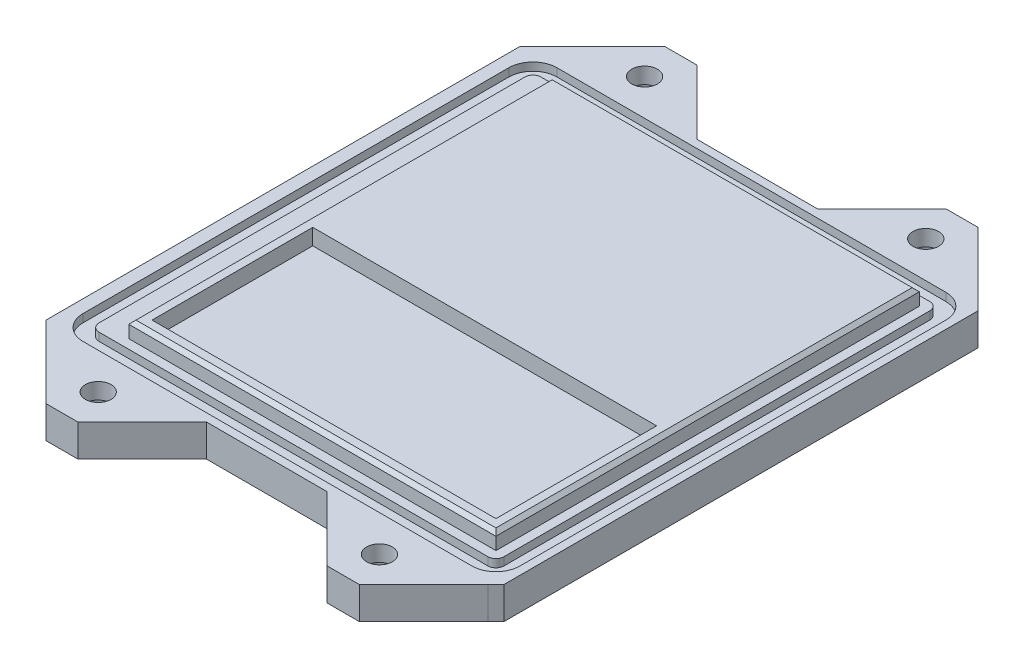
SolidWorks part; units mm, degrees
ref_plane "Front Plane" through (0, 0, 0) normal (0, 0, 1) x (1, 0, 0)
ref_plane "Top Plane" through (0, 0, 0) normal (0, 1, 0) x (1, 0, 0)
ref_plane "Right Plane" through (0, 0, 0) normal (1, 0, 0) x (0, 0, -1)
sketch "Sketch2" plane through (0, 0, 0) normal (0, 1, 0) x (1, 0, 0)
  line L1 (-44.7854, -24.8803) -> (11.2146, -24.8803)
  line L2 (-44.7854, -24.8803) -> (-44.7854, 36.1197)
  line L3 (-44.7854, 36.1197) -> (11.2146, 36.1197)
  line L4 (11.2146, -24.8803) -> (11.2146, 36.1197)
  dimension "D1" = 61
  dimension "D2" = 56
extrude "Boss-Extrude1" add sketch "Sketch2" along normal mid plane 4
sketch "Sketch3" plane through (0, 2, 0) normal (0, 1, 0) x (1, 0, 0)
  line L1 (-38.7854, 32.1197) -> (7.2146, 32.1197)
  line L2 (-38.7854, 32.1197) -> (-38.7854, -20.8803)
  line L3 (-38.7854, -20.8803) -> (7.2146, -20.8803)
  line L4 (7.2146, 32.1197) -> (7.2146, -20.8803)
  dimension "D1" = 4
  dimension "D2" = 4
  dimension "D3" = 6
  dimension "D4" = 4
extrude "Boss-Extrude4" add sketch "Sketch3" along normal blind 2
sketch "Sketch4" plane through (-44.7854, 0, 0) normal (-1, 0, 0) x (0, 0, 1)
  line L1 (-36.1197, -2) -> (24.8803, -2)
  line L2 (-36.1197, -2) -> (-36.1197, 2)
  line L3 (-36.1197, 2) -> (24.8803, 2)
  line L4 (24.8803, -2) -> (24.8803, 2)
extrude "Boss-Extrude5" add sketch "Sketch4" along normal blind 1
sketch "Sketch5" plane through (0, -2, 0) normal (0, -1, 0) x (1, 0, 0)
  line L0 (11.2146, -36.1197) -> (-45.7854, -36.1197) construction
  line L1 (3.2146, -36.1197) -> (-2.7854, -36.1197)
  line L2 (3.2146, -36.1197) -> (3.2146, -43.1197)
  line L3 (3.2146, -43.1197) -> (-2.7854, -43.1197)
  line L4 (-2.7854, -36.1197) -> (-2.7854, -43.1197)
  line L5 (-45.7854, 24.8803) -> (11.2146, 24.8803) construction
  line L6 (-37.7854, -36.1197) -> (-31.7854, -36.1197)
  line L7 (-37.7854, -36.1197) -> (-37.7854, -43.1197)
  line L8 (-37.7854, -43.1197) -> (-31.7854, -43.1197)
  line L9 (-31.7854, -36.1197) -> (-31.7854, -43.1197)
  line L10 (3.2146, 24.8803) -> (-2.7854, 24.8803)
  line L11 (3.2146, 24.8803) -> (3.2146, 31.8803)
  line L12 (3.2146, 31.8803) -> (-2.7854, 31.8803)
  line L13 (-2.7854, 24.8803) -> (-2.7854, 31.8803)
  line L15 (-37.7854, 24.8803) -> (-31.7854, 24.8803)
  line L16 (-37.7854, 24.8803) -> (-37.7854, 31.8803)
  line L17 (-37.7854, 31.8803) -> (-31.7854, 31.8803)
  line L18 (-31.7854, 24.8803) -> (-31.7854, 31.8803)
  circle A0 centre (0.2146, -39.6197) radius 1.6
  circle A1 centre (-34.7854, -39.6197) radius 1.6
  circle A2 centre (-34.7854, 28.3803) radius 1.6
  circle A3 centre (0.2146, 28.3803) radius 1.6
  dimension "D4" = 3
  dimension "D9" = 3.2
  dimension "D10" = 3.2
  dimension "D17" = 3.2
  dimension "D18" = 3.2
  dimension "D1" = 8
  dimension "D2" = 6
  dimension "D3" = 7
  dimension "D5" = 3.5
  dimension "D6" = 8
  dimension "D7" = 7
  dimension "D8" = 6
  dimension "D11" = 8
  dimension "D12" = 8
  dimension "D13" = 6
  dimension "D14" = 6
  dimension "D15" = 7
  dimension "D16" = 7
extrude "Boss-Extrude7" add sketch "Sketch5" against normal blind 4
sketch "Sketch10" plane through (0, 2, 0) normal (0, 1, 0) x (1, 0, 0)
  line L0 (6.1446, -23.8803) -> (7.1799, -23.8803)
  line L1 (6.1446, -23.8803) -> (-44.1854, -23.8803)
  line L3 (5.8967, -21.8803) -> (-42.1854, -21.8803)
  line L4 (-44.1854, -23.8803) -> (-44.1854, -21.4264)
  line L6 (-42.1854, -21.8803) -> (-42.1854, 33.1197)
  line L7 (-41.0657, 35.1197) -> (-44.1854, 35.1197)
  line L8 (-44.1854, -21.4264) -> (-44.1854, 35.1197)
  line L9 (-41.0657, 35.1197) -> (10.2146, 35.1197)
  line L11 (-42.1854, 33.1197) -> (8.2146, 33.1197)
  line L12 (10.2146, 35.1197) -> (10.2146, 33.0745)
  line L14 (10.2146, 33.0745) -> (10.2146, -23.8803)
  line L15 (10.2146, -23.8803) -> (7.1799, -23.8803)
  line L16 (8.2146, 33.1197) -> (8.2146, -21.8803)
  line L17 (5.8967, -21.8803) -> (8.2146, -21.8803)
  dimension "D1" = 2
  dimension "D2" = 2
  dimension "D3" = 2
  dimension "D4" = 2
  dimension "D5" = 2
  dimension "D6" = 1.6
  dimension "D7" = 1
  dimension "D8" = 1
  dimension "D9" = 1
extrude "Cut-Extrude1" cut sketch "Sketch10" against normal blind 1
sketch "r" plane through (0, -2, 0) normal (0, -1, 0) x (1, 0, 0)
  text T0 "XB1"
extrude "Cut-Extrude2" [suppressed] cut sketch "r" against normal blind 0.1
chamfer "Chamfer1" distance 7 angle 45 1 edges at (3.2146, 0, -36.1197)
chamfer "Chamfer2" distance 7 angle 45 1 edges at (-2.7854, 0, -36.1197)
chamfer "Chamfer3" distance 7 angle 45 6 edges at (-2.7854, 0, 24.8803) (3.2146, 0, 24.8803) (-31.7854, 0, 24.8803) (-37.7854, 0, 24.8803) (-37.7854, 0, -36.1197) (-31.7854, 0, -36.1197)
sketch "Sketch11" plane through (0, -2, 0) normal (0, -1, 0) x (1, 0, 0)
  circle A0 centre (-34.7854, 28.3803) radius 3.1
  circle A1 centre (0.2146, 28.3803) radius 3.1
  circle A2 centre (0.2146, -39.6197) radius 3.1
  circle A3 centre (-34.7854, -39.6197) radius 3.1
  dimension "D1" = 6.2
extrude "Cut-Extrude3" cut sketch "Sketch11" against normal blind 2
chamfer "Chamfer4" [suppressed] distance 1 angle 45
chamfer "Chamfer5" distance 1 angle 45 4 edges at (-45.7854, 0, -36.1197) (11.2146, 0, -36.1197) (11.2146, 0, 24.8803) (-45.7854, 0, 24.8803)
sketch "Sketch12" plane through (0, -2, 0) normal (0, -1, 0) x (1, 0, 0)
  line L0 (-31.7854, 31.8803) -> (-32.7854, 32.8803)
  line L1 (-37.7854, 31.8803) -> (-36.7854, 32.8803)
  line L2 (-32.7854, 32.8803) -> (-36.7854, 32.8803)
  line L3 (-37.7854, 31.8803) -> (-31.7854, 31.8803)
  line L4 (3.2146, 31.8803) -> (2.2146, 32.8803)
  line L5 (-2.7854, 31.8803) -> (-1.7854, 32.8803)
  line L6 (3.2146, 31.8803) -> (-2.7854, 31.8803)
  line L7 (-1.7854, 32.8803) -> (2.2146, 32.8803)
  line L8 (-2.7854, -43.1197) -> (-1.7854, -44.1197)
  line L9 (-1.0098, -44.1197) -> (2.2146, -44.1197)
  line L10 (3.2146, -43.1197) -> (2.2146, -44.1197)
  line L11 (-1.0098, -44.1197) -> (-1.7854, -44.1197)
  line L12 (-2.7854, -43.1197) -> (3.2146, -43.1197)
  line L13 (-31.7854, -43.1197) -> (-32.7854, -44.1197)
  line L14 (-37.7854, -43.1197) -> (-36.7854, -44.1197)
  line L15 (-36.7854, -44.1197) -> (-32.7854, -44.1197)
  line L16 (-37.7854, -43.1197) -> (-31.7854, -43.1197)
extrude "Boss-Extrude8" add sketch "Sketch12" against normal blind 4
sketch "Sketch13" plane through (0, 4, 0) normal (0, 1, 0) x (1, 0, 0)
  line L0 (7.2146, 32.1197) -> (-38.7854, 32.1197) construction
  line L1 (-38.7854, -20.8803) -> (-38.6854, -20.8803)
  line L2 (-38.7854, -20.8803) -> (-38.7854, 32.1197)
  line L3 (-38.7854, 32.1197) -> (-38.6854, 32.1197)
  line L4 (-38.6854, -20.7803) -> (-38.6854, 32.0197)
  line L6 (7.2146, -20.8803) -> (-38.6854, -20.8803)
  line L7 (7.2146, -20.8803) -> (7.2146, -20.7803)
  line L8 (7.1146, -20.7803) -> (-38.6854, -20.7803)
  line L10 (7.2146, 32.1197) -> (-38.6854, 32.1197)
  line L11 (7.2146, 32.1197) -> (7.2146, 32.0197)
  line L12 (7.1146, 32.0197) -> (-38.6854, 32.0197)
  line L15 (7.2146, -20.7803) -> (7.2146, 32.0197)
  line L17 (7.1146, -20.7803) -> (7.1146, 32.0197)
  dimension "D1" = 0.1
  dimension "D2" = 0.1
  dimension "D3" = 0.1
  dimension "D4" = 0.1
extrude "Cut-Extrude4" cut sketch "Sketch13" against normal blind 2
chamfer "Chamfer6" distance 0.5 angle 45 4 edges at (-15.7854, 4, -32.0197) (7.1146, 4, -5.6197) (-15.7854, 4, 20.7803) (-38.6854, 4, -5.6197)
sketch "Sketch14" plane through (0, -2, 0) normal (0, -1, 0) x (1, 0, 0)
  line L1 (-41.7854, -4.8197) -> (-39.5561, -4.8197)
  line L2 (-41.7854, -4.8197) -> (-41.7854, -6.4197)
  line L3 (-41.7854, -6.4197) -> (-39.5561, -6.4197)
  line L4 (-39.5561, -4.8197) -> (-39.5561, -6.4197)
  line L6 (-45.7854, -35.1197) -> (-45.7854, 23.8803) construction
  point P4 (-41.7854, -5.6197)
  point P7 (-45.7854, -5.6197)
  dimension "D1" = 1.6
  dimension "D2" = 0
  dimension "D3" = 4
extrude "Cut-Extrude5" cut sketch "Sketch14" against normal blind 0.4
chamfer "Chamfer7" distance 0.4 angle 45 4 edges at (-40.6707, -1.6, -4.8197) (-39.5561, -1.6, -5.6197) (-40.6707, -1.6, -6.4197) (-41.7854, -1.6, -5.6197)
sketch "Sketch15" plane through (0, 4, 0) normal (0, 1, 0) x (1, 0, 0)
  line L1 (-37.1854, -19.2803) -> (5.6146, -19.2803)
  line L2 (-37.1854, -19.2803) -> (-37.1854, 0.7197)
  line L3 (-37.1854, 0.7197) -> (5.6146, 0.7197)
  line L4 (5.6146, -19.2803) -> (5.6146, 0.7197)
  dimension "D1" = 1
  dimension "D2" = 1
  dimension "D3" = 1
  dimension "D4" = 20
extrude "Cut-Extrude6" cut sketch "Sketch15" against normal blind 2
sketch "Sketch17" plane through (0, 4, 0) normal (0, 1, 0) x (1, 0, 0)
  line L1 (7.0646, 31.9697) -> (-38.6354, 31.9697)
  line L2 (7.0646, 31.9697) -> (7.0646, -20.7303)
  line L3 (7.0646, -20.7303) -> (-38.6354, -20.7303)
  line L4 (-38.6354, 31.9697) -> (-38.6354, -20.7303)
  line L5 (39.6903, 50.7811) -> (-65.6876, 50.7811)
  line L6 (39.6903, 50.7811) -> (39.6903, -39.604)
  line L7 (39.6903, -39.604) -> (-65.6876, -39.604)
  line L8 (-65.6876, 50.7811) -> (-65.6876, -39.604)
  dimension "D1" = 52.75
  dimension "D2" = 45.7
  dimension "D3" = 45.75
  dimension "D4" = 52.7
extrude "Cut-Extrude7" cut sketch "Sketch17" against normal blind 2
fillet "Fillet1" radius 3 4 edges at (-44.1854, 1.5, 23.8803) (10.2146, 1.5, 23.8803) (10.2146, 1.5, -35.1197) (-44.1854, 1.5, -35.1197)
sketch "Sketch18" plane through (0, -2, 0) normal (0, -1, 0) x (1, 0, 0)
  line L0 (-9.7854, -36.1197) -> (-24.7854, -36.1197) construction
  line L1 (-45.7854, -34.1197) -> (11.2146, -34.1197)
  line L2 (-47.893, -34.1197) -> (-47.893, -33.1197)
  line L3 (-45.7854, -33.1197) -> (11.2158, -33.1197)
  line L5 (-45.7854, -30.1197) -> (11.2193, -30.1197)
  line L6 (-45.7854, -29.1197) -> (11.2205, -29.1197)
  line L7 (-45.7854, -26.1197) -> (11.224, -26.1197)
  line L8 (-45.7854, -25.1197) -> (11.2252, -25.1197)
  line L9 (-45.7854, -22.1197) -> (11.2287, -22.1197)
  line L10 (-45.7854, -21.1197) -> (11.2298, -21.1197)
  line L11 (-45.7854, -18.1197) -> (11.2333, -18.1197)
  line L12 (-45.7854, -17.1197) -> (11.2345, -17.1197)
  line L13 (-45.7854, -14.1197) -> (11.238, -14.1197)
  line L14 (-45.7854, -13.1197) -> (11.2392, -13.1197)
  line L15 (-45.7854, -10.1197) -> (11.2427, -10.1197)
  line L16 (-45.7854, -9.1197) -> (11.2439, -9.1197)
  line L17 (-45.7854, -6.1197) -> (11.2474, -6.1197)
  line L18 (-45.7854, -5.1197) -> (11.2485, -5.1197)
  line L19 (-45.7854, -2.1197) -> (11.252, -2.1197)
  line L20 (-45.7854, -1.1197) -> (11.2532, -1.1197)
  line L21 (-45.7854, 1.8803) -> (11.2567, 1.8803)
  line L22 (-45.7854, 2.8803) -> (11.2579, 2.8803)
  line L23 (-45.7854, 5.8803) -> (11.2614, 5.8803)
  line L24 (-45.7854, 6.8803) -> (11.2626, 6.8803)
  line L25 (-45.7854, 9.8803) -> (11.2661, 9.8803)
  line L26 (-45.7854, 10.8803) -> (11.2672, 10.8803)
  line L27 (-45.7854, 13.8803) -> (11.2707, 13.8803)
  line L28 (-45.7854, 14.8803) -> (11.2719, 14.8803)
  line L29 (-45.7854, 17.8803) -> (11.2754, 17.8803)
  line L30 (-45.7854, 18.8803) -> (11.2766, 18.8803)
  line L31 (-45.7854, 21.8803) -> (11.2801, 21.8803)
  line L32 (-45.7854, 22.8803) -> (11.2813, 22.8803)
  line L36 (-39.5561, -6.1197) -> (-39.5561, -5.1197)
  line L37 (-45.7854, -34.1197) -> (-45.7854, -33.1197)
  line L38 (-45.7854, -35.1197) -> (-45.7854, 23.8803) construction
  line L39 (11.2813, 22.8803) -> (11.2801, 21.8803)
  line L40 (11.2146, 23.8803) -> (11.2146, -35.1197) construction
  line L41 (-45.7854, -30.1197) -> (-45.7854, -29.1197)
  line L42 (-45.7854, -26.1197) -> (-45.7854, -25.1197)
  line L43 (-45.7854, -22.1197) -> (-45.7854, -21.1197)
  line L44 (-45.7854, -18.1197) -> (-45.7854, -17.1197)
  line L45 (-45.7854, -14.1197) -> (-45.7854, -13.1197)
  line L46 (-45.7854, -10.1197) -> (-45.7854, -9.1197)
  line L47 (-45.7854, -6.1197) -> (-45.7854, -5.1197)
  line L48 (-45.7854, -2.1197) -> (-45.7854, -1.1197)
  line L49 (-45.7854, 1.8803) -> (-45.7854, 2.8803)
  line L50 (-45.7854, 5.8803) -> (-45.7854, 6.8803)
  line L51 (-45.7854, 9.8803) -> (-45.7854, 10.8803)
  line L52 (-45.7854, 13.8803) -> (-45.7854, 14.8803)
  line L53 (-45.7854, 17.8803) -> (-45.7854, 18.8803)
  line L54 (-45.7854, 21.8803) -> (-45.7854, 22.8803)
  line L55 (11.2766, 18.8803) -> (11.2754, 17.8803)
  line L56 (11.2719, 14.8803) -> (11.2707, 13.8803)
  line L57 (11.2672, 10.8803) -> (11.2661, 9.8803)
  line L58 (11.2626, 6.8803) -> (11.2614, 5.8803)
  line L59 (11.2532, -1.1197) -> (11.252, -2.1197)
  line L60 (11.2485, -5.1197) -> (11.2474, -6.1197)
  line L61 (11.2439, -9.1197) -> (11.2427, -10.1197)
  line L62 (11.2392, -13.1197) -> (11.238, -14.1197)
  line L63 (11.2345, -17.1197) -> (11.2333, -18.1197)
  line L64 (11.2298, -21.1197) -> (11.2287, -22.1197)
  line L65 (11.2252, -25.1197) -> (11.224, -26.1197)
  line L66 (11.2205, -29.1197) -> (11.2193, -30.1197)
  line L67 (11.2158, -33.1197) -> (11.2146, -34.1197)
  line L68 (-38.5561, -6.1197) -> (-38.5561, -5.1197)
  line M40 (-45.7854, 23.8803) -> (-45.7854, -35.1197)
  line M50 (11.2146, -35.1197) -> (11.2146, 23.8803)
  dimension "D1" = 1
  dimension "D2" = 2
  dimension "D4" = 1
  dimension "D3" = 15
extrude "Boss-Extrude9" [suppressed] add sketch "Sketch18" along normal blind 1 contours L8 L7 M40 M50 | L12 L11 M40 M50 | L16 L15 M40 M50 | L20 L19 M40 M50 | L24 L23 M40 M50 | L28 L27 M40 M50 | L32 L31 M40 M50 | L3 L1 M40 M50
chamfer "Chamfer8" [suppressed] distance 1 angle 45
chamfer "Chamfer9" [suppressed] distance 1 angle 45
fillet "Fillet2" radius 1 4 edges at (-42.1854, 1.5, -33.1197) (-42.1854, 1.5, 21.8803) (8.2146, 1.5, 21.8803) (8.2146, 1.5, -33.1197)
